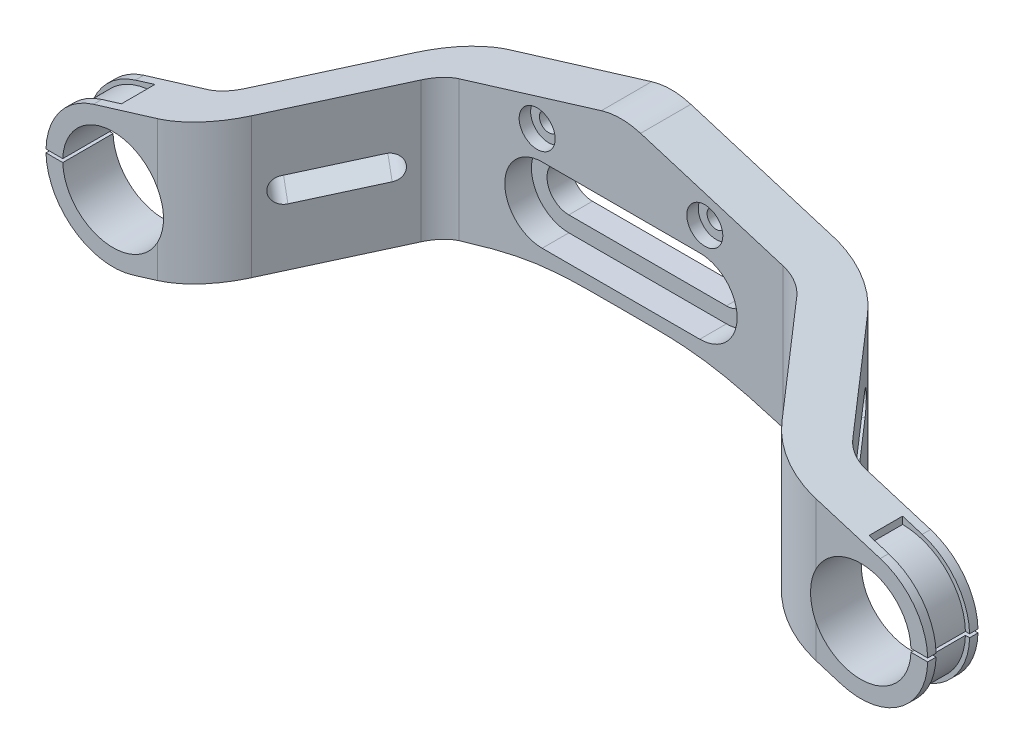
SolidWorks part; units mm, degrees
ref_plane "Front" through (0, 0, 0) normal (0, 0, 1) x (1, 0, 0)
ref_plane "Top" through (0, 0, 0) normal (0, 1, 0) x (1, 0, 0)
ref_plane "Right" through (0, 0, 0) normal (1, 0, 0) x (0, 0, -1)
sketch "Sketch1" plane through (0, 0, 0) normal (0, 1, 0) x (1, 0, 0)
  line L0 (0, 0) -> (-96.6846, 0)
  line L1 (-134.9868, -17.8606) -> (-181.1332, -72.8558)
  line L2 (-196.4541, -80) -> (-280, -80)
  arc A0 (-96.6846, 0) -> (-134.9868, -17.8606) centre (-96.6846, -50) ccw
  arc A1 (-181.1332, -72.8558) -> (-196.4541, -80) centre (-196.4541, -60) cw
  point P9 (-120, 0)
  dimension "D1" = 120
  dimension "D4" = 50
  dimension "D5" = 20
  dimension "D2" = 80
  dimension "D3" = 280
  dimension "D6" = 50
extrude "Extrude-Thin1" add sketch "Sketch1" against normal blind 150 thin thin type one direction reverse wall 30
sketch "Sketch2" plane through (0, 0, 0) normal (0, 0, 1) x (1, 0, 0)
  line L0 (0, 0) -> (-234.6765, -71.7478)
  line L2 (0, -150) -> (0, 0) construction
  line L3 (0, -100) -> (0, 0)
  line L4 (0, 0) -> (-96.6846, 0) construction
  line L5 (-196.4541, -150) -> (-280, -150) construction
  line L6 (-211.2868, -148.2522) -> (-95, -112.6998)
  line L7 (44.3467, -100) -> (-44.3467, -100) construction
  line L8 (-55.2954, -100.5608) -> (-134.1815, -124.6787) construction
  arc A0 (-234.6765, -71.7478) -> (-211.2868, -148.2522) centre (-222.9816, -110) ccw
  spline S0 degree 3 poles (-95, -112.6998) (-51.5325, -99.4104) (-36.9555, -100) (0, -100) knots 0 0 0 0 1 1 1 1
  dimension "D2" = 40
  dimension "D1" = 17
  dimension "D3" = 100
  dimension "D4" = 95
extrude "Cut-Extrude1" cut sketch "Sketch2" along normal through all flip side to cut
sketch "Sketch3" plane through (0, 0, 110) normal (0, 0, 1) x (1, 0, 0)
  circle A0 centre (-222.9816, -110) radius 30
  dimension "D1" = 60
extrude "Cut-Extrude2" cut sketch "Sketch3" against normal through all
sketch "Sketch4" plane through (0, 0, 110) normal (0, 0, 1) x (1, 0, 0)
  line L0 (-222.9816, -68.1723) -> (-222.9816, -72.5)
  line L1 (-196.4541, -60.0621) -> (-234.6765, -71.7478) construction
  line L2 (-234.6765, -71.7478) -> (-222.9816, -68.1723)
  line L3 (-222.9816, -147.5) -> (-222.9816, -150)
  arc A0 (-234.6765, -71.7478) -> (-211.2868, -148.2522) centre (-222.9816, -110) ccw construction
  arc A1 (-234.6765, -71.7478) -> (-222.9816, -150) centre (-222.9816, -110) ccw
  arc A2 (-222.9816, -72.5) -> (-222.9816, -147.5) centre (-222.9816, -110) ccw
  dimension "D1" = 2.5
extrude "Cut-Extrude3" cut sketch "Sketch4" against normal mid plane 20 from offset 15 offset against normal yes
sketch "Sketch5" plane through (0, 0, 110) normal (0, 0, 1) x (1, 0, 0)
  line L5 (-322.9816, -109) -> (-222.9816, -109)
  line L6 (-322.9816, -109) -> (-322.9816, -111)
  line L7 (-322.9816, -111) -> (-222.9816, -111)
  line L8 (-222.9816, -109) -> (-222.9816, -111)
  dimension "D1" = 2
  dimension "D2" = 100
extrude "Cut-Extrude4" cut sketch "Sketch5" against normal through all
hole_wizard "CBORE SLOT for M24 Hex Head Bolt1" positions "Sketch6" profile "Sketch7" size "M24" standard "ANSI Metric" slot yes end condition through all
sketch "Sketch6" plane through (0, 0, 30) normal (0, 0, 1) x (1, 0, 0)
  line L0 (0, -100) -> (0, 0) construction
  line L1 (-60, -70) -> (60, -70) construction
  point P10 (0, -70)
  dimension "D1" = 120
  dimension "D2" = 30
sketch "Sketch7" plane through (0, -70, 30) normal (1, 0, 0) x (0, -1, 0)
  line L0 (0, 0) -> (0, 30)
  line L1 (0, 30) -> (13, 30)
  line L3 (13, 30) -> (13, 15.9)
  line L4 (13, 15.9) -> (22.285, 15.9)
  line L5 (22.285, 15.9) -> (22.285, 0)
  line L7 (22.285, 0) -> (0, 0)
  line L11 (0, -6.35) -> (0, 107.95) construction
  dimension "Thru Hole Dia." = 26
  dimension "Thru Hole Depth" = 30
  dimension "C'Bore Dia." = 44.57
  dimension "C'Bore Depth" = 15.9
hole_wizard "CBORE for M10 Hex Head Bolt1" positions "Sketch9" profile "Sketch10" counterbore size "M10" standard "ANSI Metric" end condition through all
sketch "Sketch9" plane through (0, 0, 30) normal (0, 0, 1) x (1, 0, 0)
  line L0 (0, -47.715) -> (0, 0) construction
  point P0 (-50, -32)
  dimension "D1" = 50
  dimension "D2" = 32
sketch "Sketch10" plane through (-50, -32, 30) normal (1, 0, 0) x (0, -1, 0)
  line L0 (0, 0) -> (0, 30)
  line L1 (0, 30) -> (5.5, 30)
  line L3 (5.5, 30) -> (5.5, 6.85)
  line L4 (5.5, 6.85) -> (10.74, 6.85)
  line L5 (10.74, 6.85) -> (10.74, 0)
  line L7 (10.74, 0) -> (0, 0)
  line L11 (0, -6.35) -> (0, 107.95) construction
  dimension "Thru Hole Dia." = 11
  dimension "Thru Hole Depth" = 30
  dimension "C'Bore Dia." = 21.48
  dimension "C'Bore Depth" = 6.85
sketch "Sketch11" plane through (-47.4376, 0, -39.8048) normal (0.766, 0, 0.6428) x (0.6428, 0, -0.766)
  line L0 (-158.3426, -87.4483) -> (-114.1871, -78.7708) construction
  line L1 (-159.7888, -80.089) -> (-115.6334, -71.4116)
  line L2 (-156.8963, -94.8075) -> (-112.7409, -86.1301)
  line L3 (-100.4499, -34.2435) -> (-172.2409, -48.3519) construction
  line L4 (-114.1871, -78.7708) -> (-100.4499, -76.0712) construction
  line L5 (-100.4499, -117.8989) -> (-100.4499, -34.2435) construction
  arc A0 (-159.7888, -80.089) -> (-156.8963, -94.8075) centre (-158.3426, -87.4483) ccw
  arc A1 (-112.7409, -86.1301) -> (-115.6334, -71.4116) centre (-114.1871, -78.7708) ccw
  point P2 (-136.2649, -83.1095)
  dimension "D1" = 45
  dimension "D2" = 15
  dimension "D3" = 36.5
extrude "Cut-Extrude5" cut sketch "Sketch11" against normal through all
mirror "Mirror1" about plane through (0, 0, 0) normal (1, 0, 0) of bodies 108
fillet "Fillet2" radius 40 1 edges at (0, 0, 15)
